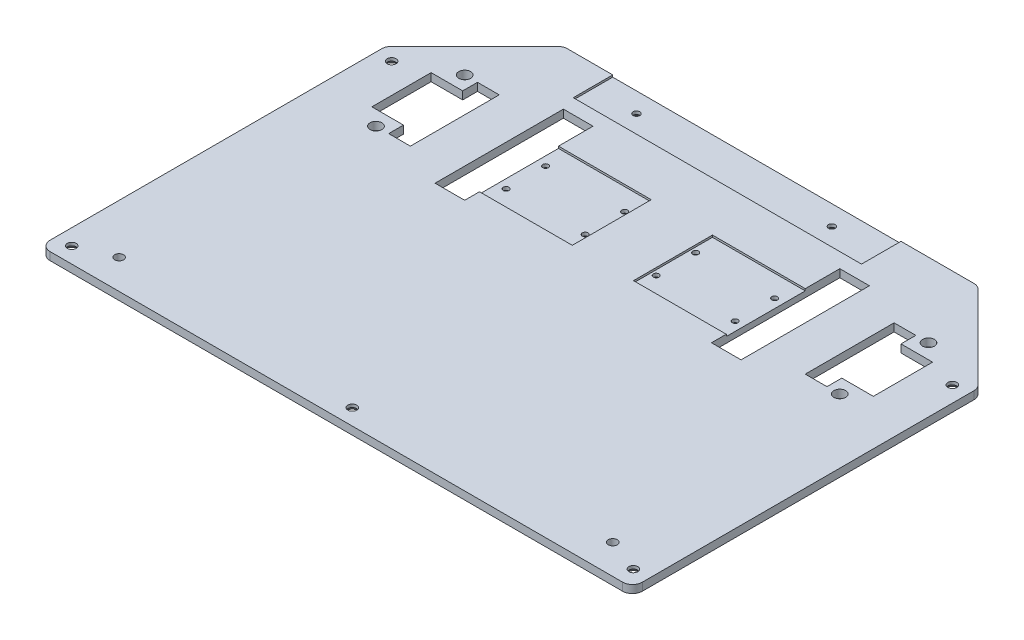
SolidWorks part; units mm, degrees
material "Acier non allié"
ref_plane "Front" through (0, 0, 0) normal (0, 0, 1) x (1, 0, 0)
ref_plane "Top" through (0, 0, 0) normal (0, 1, 0) x (1, 0, 0)
ref_plane "Right" through (0, 0, 0) normal (1, 0, 0) x (0, 0, -1)
sketch "Main scetch" plane through (0, 0, 0) normal (0, 1, 0) x (1, 0, 0)
  line L0 (-150, 0) -> (150, 0)
  line L1 (0, 0) -> (150, 0) construction
  line L2 (0, 0) -> (0, 220) construction
  line L3 (0, 220) -> (150, 220) construction
  line L4 (150, 0) -> (150, 220) construction
  line L5 (150, 0) -> (150, 175)
  line L6 (150, 175) -> (105, 220)
  line L10 (105, 220) -> (-105, 220)
  line L11 (-150, 0) -> (-150, 175)
  line L12 (-150, 175) -> (-105, 220)
  dimension "D1" = 150
  dimension "D2" = 220
  dimension "D3" = 45
  dimension "D4" = 45
extrude "Main extrusion" add sketch "Main scetch" along normal blind 4
fillet "Corner leave" radius 5 6 edges at (-150, 2, 0) (150, 2, -175) (105, 2, -220) (150, 2, 0) (-105, 2, -220) (-150, 2, -175)
sketch "Esquisse2" plane through (0, 4, 0) normal (0, 1, 0) x (1, 0, 0)
  line L0 (-145, 0) -> (145, 0) construction
  line L1 (150, 5) -> (150, 172.9289) construction
  line L2 (148.5355, 176.4645) -> (106.4645, 218.5355) construction
  line L3 (102.9289, 220) -> (-102.9289, 220) construction
  line L4 (-106.4645, 218.5355) -> (-148.5355, 176.4645) construction
  line L5 (-150, 172.9289) -> (-150, 5) construction
  line L6 (-145, 0) -> (145, 0) construction
  line L7 (150, 5) -> (150, 172.9289) construction
  line L8 (148.5355, 176.4645) -> (106.4645, 218.5355) construction
  line L9 (102.9289, 220) -> (-102.9289, 220) construction
  line L10 (-106.4645, 218.5355) -> (-148.5355, 176.4645) construction
  line L11 (-150, 172.9289) -> (-150, 5) construction
  line L12 (0, 0) -> (0, 238.9669) construction
  line L13 (0, 160) -> (165.6987, 160) construction
  line L14 (70, 230.4421) -> (70, 102.0601) construction
  line L15 (62.5, 192.5) -> (77.5, 192.5)
  line L16 (62.5, 192.5) -> (62.5, 127.5)
  line L17 (62.5, 127.5) -> (77.5, 127.5)
  line L18 (77.5, 192.5) -> (77.5, 127.5)
  line L19 (100, 137.5) -> (100, 182.5)
  line L20 (100, 182.5) -> (111, 182.5)
  line L22 (127, 175) -> (127, 145)
  line L23 (100, 137.5) -> (111, 137.5)
  line L35 (111, 182.5) -> (111, 175)
  line L36 (111, 175) -> (127, 175)
  line L37 (111, 137.5) -> (111, 145)
  line L38 (111, 145) -> (127, 145)
  line L39 (-111, 137.5) -> (-111, 145)
  line L40 (-100, 137.5) -> (-111, 137.5)
  line L41 (-100, 137.5) -> (-100, 182.5)
  line L42 (-100, 182.5) -> (-111, 182.5)
  line L43 (-111, 182.5) -> (-111, 175)
  line L44 (-111, 175) -> (-127, 175)
  line L45 (-127, 175) -> (-127, 145)
  line L46 (-111, 145) -> (-127, 145)
  line L47 (-62.5, 127.5) -> (-77.5, 127.5)
  line L48 (-77.5, 192.5) -> (-77.5, 127.5)
  line L49 (-62.5, 192.5) -> (-77.5, 192.5)
  line L50 (-62.5, 192.5) -> (-62.5, 127.5)
  circle A0 centre (117.47, 182.47) radius 3
  circle A1 centre (117.47, 137.53) radius 3
  circle A2 centre (-117.47, 137.53) radius 3
  circle A3 centre (-117.47, 182.47) radius 3
  point P28 (127, 160)
  point P29 (100, 160)
  dimension "D12" = 6
  dimension "D1" = 60
  dimension "D2" = 65
  dimension "D3" = 70
  dimension "D4" = 15
  dimension "D5" = 27
  dimension "D6" = 45
  dimension "D7" = 100
  dimension "D8" = 11
  dimension "D9" = 30
  dimension "D10" = 17.47
  dimension "D11" = 22.47
extrude "Enlèv. mat.-Extru.1" cut sketch "Esquisse2" against normal through all
sketch "Esquisse8" plane through (0, 4, 0) normal (0, 1, 0) x (1, 0, 0)
  line L0 (-150, 172.9289) -> (-150, 5) construction
  line L1 (-145, 0) -> (145, 0) construction
  line L3 (150, 5) -> (150, 172.9289) construction
  circle A0 centre (-125, 15) radius 1.5
  circle A1 centre (125, 15) radius 1.5
  dimension "D1" = 3
  dimension "D4" = 3
  dimension "D6" = 25
  dimension "D2" = 25
  dimension "D3" = 15
  dimension "D5" = 15
hole_wizard "Dégagement M41" positions "Esquisse16" profile "Esquisse17" hole size "M4" standard "ISO" end condition through all
sketch "Esquisse16" plane through (0, 4, 0) normal (0, 1, 0) x (1, 0, 0)
  point P0 (-125, 15)
  point P3 (125, 15)
sketch "Esquisse17" plane through (-125, 4, -15) normal (1, 0, 0) x (0, 0, 1)
  line L0 (0, 0) -> (0, 4)
  line L1 (0, 4) -> (2.25, 4)
  line L2 (2.25, 4) -> (2.25, 0)
  line L5 (2.25, 0) -> (0, 0)
  line L11 (0, -6.35) -> (0, 107.95) construction
  dimension "Diamètre du perçage jusqu'au prochain" = 4.5
  dimension "Profondeur du perçage jusqu'au prochain" = 4
sketch "Esquisse18" plane through (0, 4, 0) normal (0, 1, 0) x (1, 0, 0)
  line L0 (-150, 172.9289) -> (-150, 5) construction
  line L1 (-145, 0) -> (145, 0) construction
  line L3 (150, 5) -> (150, 172.9289) construction
  circle A0 centre (-142, 8) radius 1
  circle A1 centre (-142, 170) radius 1
  circle A4 centre (142, 170) radius 1
  circle A5 centre (142, 8) radius 1
  circle A6 centre (0, 8) radius 1.5
  dimension "D1" = 2
  dimension "D2" = 2
  dimension "D3" = 3
  dimension "D4" = 8
  dimension "D5" = 2
  dimension "D6" = 2
  dimension "D7" = 8
  dimension "D8" = 8
  dimension "D9" = 170
  dimension "D10" = 8
  dimension "D15" = 8
  dimension "D16" = 170
  dimension "D17" = 8
  dimension "D18" = 8
sketch "Esquisse23" plane through (0, 4, 0) normal (0, 1, 0) x (1, 0, 0)
  line L0 (-62.5, 127.5) -> (-62.5, 192.5) construction
  line L1 (-62.5, 175) -> (-15.5, 175)
  line L2 (-62.5, 175) -> (-62.5, 135)
  line L3 (-62.5, 135) -> (-15.5, 135)
  line L4 (-15.5, 175) -> (-15.5, 135)
  line L6 (-62.5, 160) -> (-12.8793, 160) construction
  point P9 (-62.5, 160)
  dimension "D1" = 40
  dimension "D2" = 47
  dimension "D3" = 15
extrude "Enlèv. mat.-Extru.2" cut sketch "Esquisse23" against normal blind 1
sketch "Esquisse24" plane through (0, 3, 0) normal (0, 1, 0) x (1, 0, 0)
  line L0 (-58, 212.7511) -> (-58, 75.2489) construction
  line L1 (-62.5, 175) -> (-62.5, 135) construction
  line L2 (-15.5, 175) -> (-62.5, 175) construction
  line L3 (-18, 126.9657) -> (-18, 195.1017) construction
  line L4 (-58, 164) -> (-9.2469, 164) construction
  line L5 (-58, 144) -> (-13.1999, 144) construction
  circle A0 centre (-58, 164) radius 1
  circle A1 centre (-58, 144) radius 1
  circle A2 centre (-18, 164) radius 1
  circle A3 centre (-18, 144) radius 1
  dimension "D1" = 2
  dimension "D2" = 2
  dimension "D7" = 2
  dimension "D8" = 2
  dimension "D3" = 20
  dimension "D4" = 4.5
  dimension "D5" = 11
  dimension "D6" = 40
extrude "Enlèv. mat.-Extru.3" cut sketch "Esquisse24" against normal through all
hole_wizard "Fraisage pour vis à tête fraisée M2.51" positions "Esquisse27" profile "Esquisse28" countersink size "M2.5" standard "ISO" end condition through all
sketch "Esquisse27" plane through (0, 0, 0) normal (0, -1, 0) x (-1, 0, 0)
  point P0 (18, 164)
  point P3 (58, 164)
  point P6 (58, 144)
  point P9 (18, 144)
sketch "Esquisse28" plane through (-18, 0, -164) normal (1, 0, 0) x (0, 0, -1)
  line L0 (0, 0) -> (0, 4)
  line L1 (0, 4) -> (1.45, 4)
  line L2 (1.45, 4) -> (1.45, 1.3)
  line L3 (1.45, 1.3) -> (2.75, 0)
  line L5 (2.75, 0) -> (0, 0)
  line L6 (-1.45, 1.3) -> (-2.75, 0) construction
  line L11 (0, -6.35) -> (0, 107.95) construction
  dimension "Diamètre du perçage jusqu'au prochain" = 2.9
  dimension "Profondeur du perçage jusqu'au prochain" = 4
  dimension "Diamètre du fraisage entrant" = 5.5
  dimension "Angle du fraisage entrant" = 90
mirror "Symétrie1" about plane through (0, 0, 0) normal (1, 0, 0) of "Enlèv. mat.-Extru.3", "Fraisage pour vis à tête fraisée M2.51", "Enlèv. mat.-Extru.2"
hole_wizard "Fraisage pour vis à tête fraisée M41" positions "Esquisse30" profile "Esquisse31" countersink size "M4" standard "ISO" end condition through all
sketch "Esquisse30" plane through (0, 0, 0) normal (0, -1, 0) x (-1, 0, 0)
  point P0 (-142.0349, 8.4348)
  point P2 (0, 8.1016)
  point P4 (0, 8.1016)
  point P6 (142, 8)
  point P9 (142, 170)
  point P12 (-142, 170)
sketch "Esquisse31" plane through (142.0349, 0, -8.4348) normal (1, 0, 0) x (0, 0, -1)
  line L0 (0, 0) -> (0, 4)
  line L1 (0, 4) -> (2.25, 4)
  line L2 (2.25, 4) -> (2.25, 2.45)
  line L3 (2.25, 2.45) -> (4.7, 0)
  line L5 (4.7, 0) -> (0, 0)
  line L6 (-2.25, 2.45) -> (-4.7, 0) construction
  line L11 (0, -6.35) -> (0, 107.95) construction
  dimension "Diamètre du perçage jusqu'au prochain" = 4.5
  dimension "Profondeur du perçage jusqu'au prochain" = 4
  dimension "Diamètre du fraisage entrant" = 9.4
  dimension "Angle du fraisage entrant" = 90
sketch "Esquisse32" plane through (0, 4, 0) normal (0, 1, 0) x (1, 0, 0)
  line L0 (102.9289, 220) -> (-102.9289, 220) construction
  line L1 (-80, 220) -> (66, 220)
  line L2 (-80, 220) -> (-80, 200)
  line L3 (-80, 200) -> (66, 200)
  line L4 (66, 220) -> (66, 200)
  line L5 (150, 5) -> (150, 172.9289) construction
  dimension "D1" = 84
  dimension "D2" = 146
  dimension "D3" = 20
extrude "Enlèv. mat.-Extru.4" cut sketch "Esquisse32" against normal blind 1
sketch "Esquisse33" plane through (0, 0, 0) normal (0, -1, 0) x (1, 0, 0)
  line L4 (-80, -200) -> (-80, -220)
  line L5 (66, -200) -> (-80, -200)
  line L6 (66, -220) -> (66, -200)
  line L7 (-80, -220) -> (66, -220)
  line L8 (-80, -200) -> (-80, -220) construction
  line L9 (66, -200) -> (-80, -200) construction
  line L10 (66, -220) -> (66, -200) construction
  line L11 (-80, -220) -> (66, -220) construction
  circle A0 centre (-58, -210) radius 1
  circle A1 centre (41, -210) radius 1
  dimension "D4" = 2
  dimension "D7" = 2
  dimension "D2" = 22
  dimension "D3" = 10
  dimension "D5" = 25
  dimension "D6" = 10
  dimension "D1" = 0
extrude "Enlèv. mat.-Extru.5" cut sketch "Esquisse33" against normal through all
hole_wizard "Fraisage pour vis à tête fraisée M31" positions "Esquisse34" profile "Esquisse35" countersink size "M3" standard "ISO" end condition through all
sketch "Esquisse34" plane through (0, 0, 0) normal (0, -1, 0) x (-1, 0, 0)
  point P0 (58, 210)
  point P3 (-41, 210)
sketch "Esquisse35" plane through (-58, 0, -210) normal (1, 0, 0) x (0, 0, -1)
  line L0 (0, 0) -> (0, 4)
  line L1 (0, 4) -> (1.7, 4)
  line L2 (1.7, 4) -> (1.7, 1.45)
  line L3 (1.7, 1.45) -> (3.15, 0)
  line L5 (3.15, 0) -> (0, 0)
  line L6 (-1.7, 1.45) -> (-3.15, 0) construction
  line L11 (0, -6.35) -> (0, 107.95) construction
  dimension "Diamètre du perçage jusqu'au prochain" = 3.4
  dimension "Profondeur du perçage jusqu'au prochain" = 4
  dimension "Diamètre du fraisage entrant" = 6.3
  dimension "Angle du fraisage entrant" = 90
equation "\"WIDTH\"= 300mm'Total width of the robot"
equation "\"LENGTH\"= 220mm'Total length of the robot"
equation "\"D1@Main scetch\" = \"WIDTH\" / 2"
equation "\"D2@Main scetch\" = \"LENGTH\""
equation "\"CUT_DEPTH\"= 45mm'Depth of the cut on the edges of the plate"
equation "\"D3@Main scetch\" = \"CUT_DEPTH\""
equation "\"D4@Main scetch\" = \"CUT_DEPTH\""
equation "\"Plate_th\"= 3mm'Thickness of the plate"
equation "\"D1\"= \"Plate_th\""
